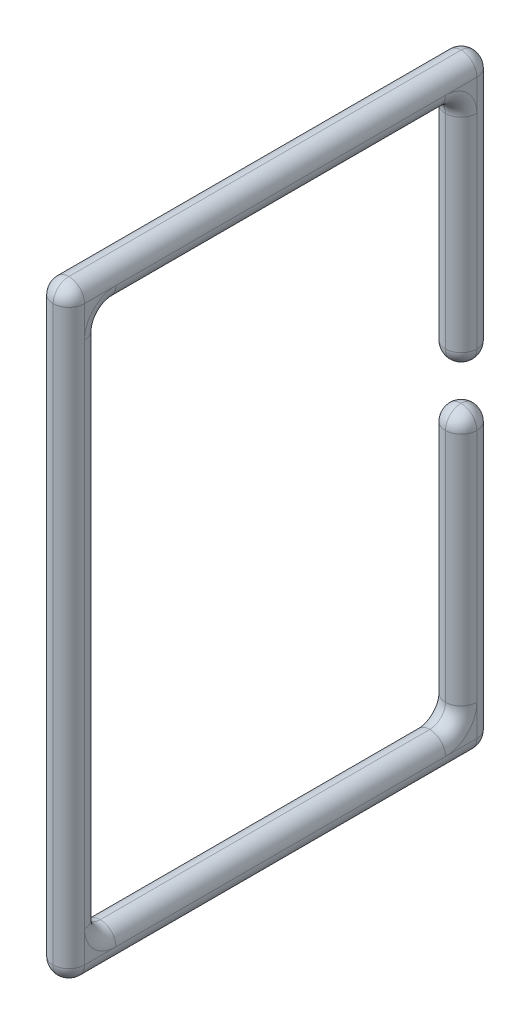
SolidWorks part; units mm, degrees
material "1.4000 (X6Cr13)"
ref_plane "Płaszczyzna przednia" through (0, 0, 0) normal (0, 0, 1) x (1, 0, 0)
ref_plane "Płaszczyzna górna" through (0, 0, 0) normal (0, 1, 0) x (1, 0, 0)
ref_plane "Płaszczyzna prawa" through (0, 0, 0) normal (1, 0, 0) x (0, 0, -1)
sketch "Szkic1" plane through (0, 0, 0) normal (0, 1, 0) x (1, 0, 0)
  line L1 (2, 2) -> (-2, 2)
  line L2 (2, 2) -> (2, -2)
  line L3 (2, -2) -> (-2, -2)
  line L4 (-2, 2) -> (-2, -2)
  line L5 (2, 2) -> (-2, -2) construction
  line L6 (2, -2) -> (-2, 2) construction
  point P0 (0, 0)
  dimension "D1" = 4
  dimension "D2" = 4
extrude "Dodanie-wyciągnięcie1" add sketch "Szkic1" along normal blind 34
sketch "Szkic2" plane through (0, 0, 2) normal (0, 0, 1) x (1, 0, 0)
  line L0 (2, 34) -> (2, 0) construction
  line L1 (-2, 34) -> (2, 34)
  line L2 (-2, 34) -> (-2, 30)
  line L3 (-2, 30) -> (2, 30)
  line L4 (2, 34) -> (2, 30)
  dimension "D1" = 4
extrude "Dodanie-wyciągnięcie2" add sketch "Szkic2" along normal blind 50
sketch "Szkic3" plane through (0, 30, 0) normal (0, -1, 0) x (1, 0, 0)
  line L0 (2, 52) -> (2, 2) construction
  line L1 (-2, 52) -> (2, 52)
  line L2 (-2, 52) -> (-2, 48)
  line L3 (-2, 48) -> (2, 48)
  line L4 (2, 52) -> (2, 48)
  dimension "D1" = 4
extrude "Dodanie-wyciągnięcie3" add sketch "Szkic3" along normal blind 73
sketch "Szkic4" plane through (0, 0, 48) normal (0, 0, -1) x (-1, 0, 0)
  line L0 (-2, -43) -> (-2, 30) construction
  line L1 (2, -43) -> (-2, -43)
  line L2 (2, -43) -> (2, -39)
  line L3 (2, -39) -> (-2, -39)
  line L4 (-2, -43) -> (-2, -39)
  dimension "D1" = 4
extrude "Dodanie-wyciągnięcie4" add sketch "Szkic4" along normal blind 50
sketch "Szkic5" plane through (0, -39, 0) normal (0, 1, 0) x (1, 0, 0)
  line L0 (-2, 2) -> (-2, -48) construction
  line L1 (2, 2) -> (-2, 2)
  line L2 (2, 2) -> (2, -2)
  line L3 (2, -2) -> (-2, -2)
  line L4 (-2, 2) -> (-2, -2)
  dimension "D1" = 4
extrude "Dodanie-wyciągnięcie5" add sketch "Szkic5" along normal blind 34
fillet "Zaokrąglenie1" radius 2 20 edges at (2, 15, 2) (2, 30, 25) (2, -4.5, 48) (2, -39, 25) (2, -22, 2) (2, -24, -2) (2, -43, 25) (2, -4.5, 52) (2, 34, 25) (2, 17, -2) (-2, 17, -2) (-2, 34, 25) (-2, -4.5, 52) (-2, -43, 25) (-2, -24, -2) (-2, -22, 2) (-2, -39, 25) (-2, -4.5, 48) (-2, 30, 25) (-2, 15, 2)
